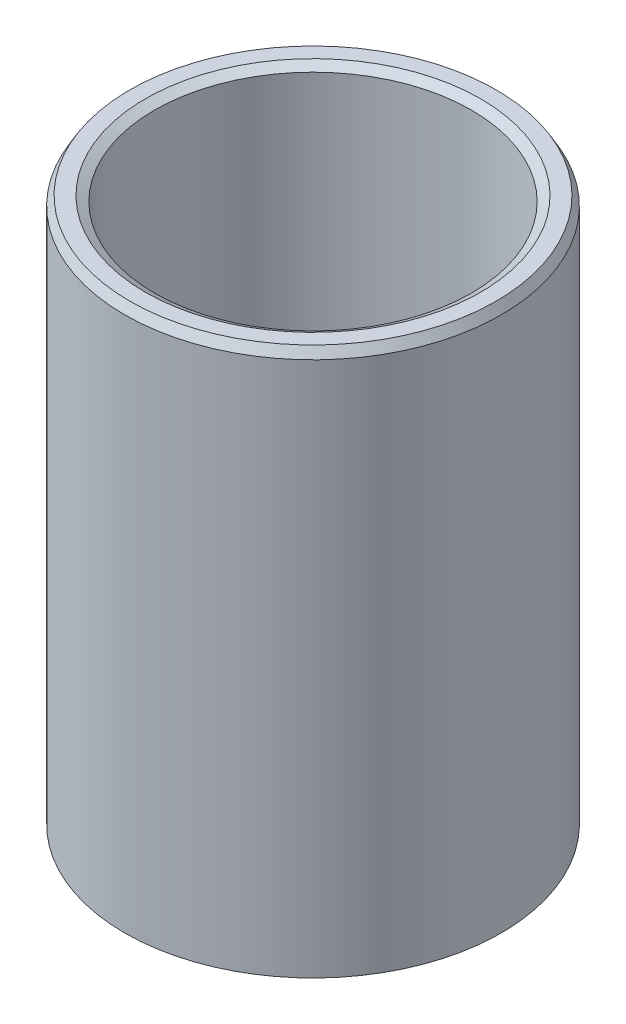
SolidWorks part; units mm, degrees
ref_plane "Front Plane" through (0, 0, 0) normal (0, 0, 1) x (1, 0, 0)
ref_plane "Top Plane" through (0, 0, 0) normal (0, 1, 0) x (1, 0, 0)
ref_plane "Right Plane" through (0, 0, 0) normal (1, 0, 0) x (0, 0, -1)
sketch "Sketch1" plane through (0, 0, 0) normal (0, 1, 0) x (1, 0, 0)
  circle A0 centre (0, 0) radius 25
  dimension "SLEEVE_OD" = 50
extrude "Boss-Extrude1" add sketch "Sketch1" along normal blind 72.9566
sketch "Sketch2" plane through (0, 0, 0) normal (0, 1, 0) x (1, 0, 0)
  circle A0 centre (0, 0) radius 21.0348
  dimension "BORE_D" = 42.0696
extrude "Cut-Extrude1" cut sketch "Sketch2" along normal through all
chamfer "Chamfer1" distance 1.2094 angle 30 4 edges at (0, 72.9566, 21.0348) (0, 0, 21.0348) (0, 0, 25) (0, 72.9566, 25) first distance on face at (0, 72.9566, 21.0348) first distance on face at (0, 0, 21.0348) first distance on face at (0, 72.9566, 25)
